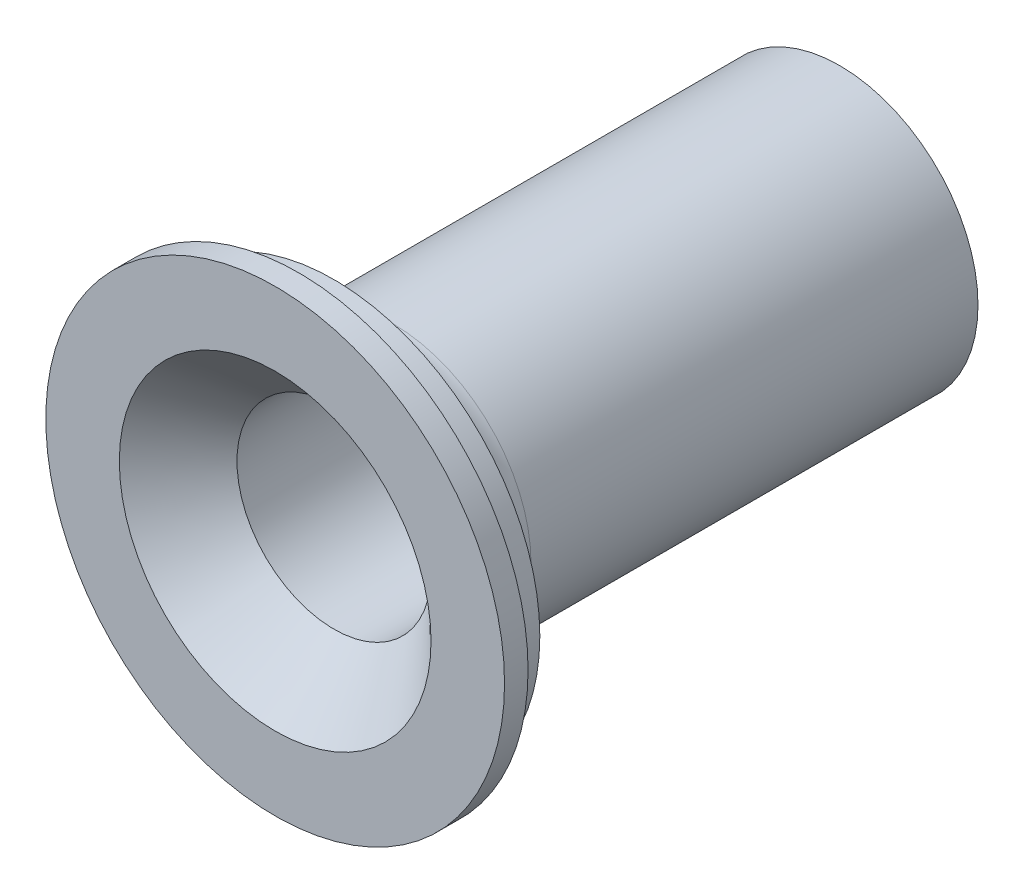
SolidWorks part; units mm, degrees
material "ABS"
ref_plane "Front" through (0, 0, 0) normal (0, 0, 1) x (1, 0, 0)
ref_plane "Top" through (0, 0, 0) normal (0, 1, 0) x (1, 0, 0)
ref_plane "Right" through (0, 0, 0) normal (1, 0, 0) x (0, 0, -1)
sketch "Szkic1" plane through (0, 0, 0) normal (0, 1, 0) x (1, 0, 0)
  line L0 (2, 46) -> (8.25, 46)
  line L1 (2, 46) -> (2, 41)
  line L2 (2, 41) -> (5.25, 41)
  line L3 (8.25, 46) -> (8.25, 48)
  line L4 (8.25, 48) -> (11.75, 48)
  line L5 (11.75, 48) -> (11.75, 10)
  line L6 (8.25, 38) -> (8.25, 5)
  line L7 (19.5, 0) -> (13.25, 0)
  line L8 (8.25, 5) -> (13.25, 0)
  line L9 (17.5, 5) -> (16.75, 5)
  line L10 (17.5, 5) -> (17.5, 2)
  line L11 (17.5, 2) -> (19.5, 2)
  line L12 (19.5, 2) -> (19.5, 0)
  line L13 (0, 0) -> (0, 48) construction
  arc A0 (8.25, 38) -> (5.25, 41) centre (5.25, 38) ccw
  arc A1 (11.75, 10) -> (16.75, 5) centre (16.75, 10) ccw
revolve "Obrót1" add sketch "Szkic1" angle 360 about L13
